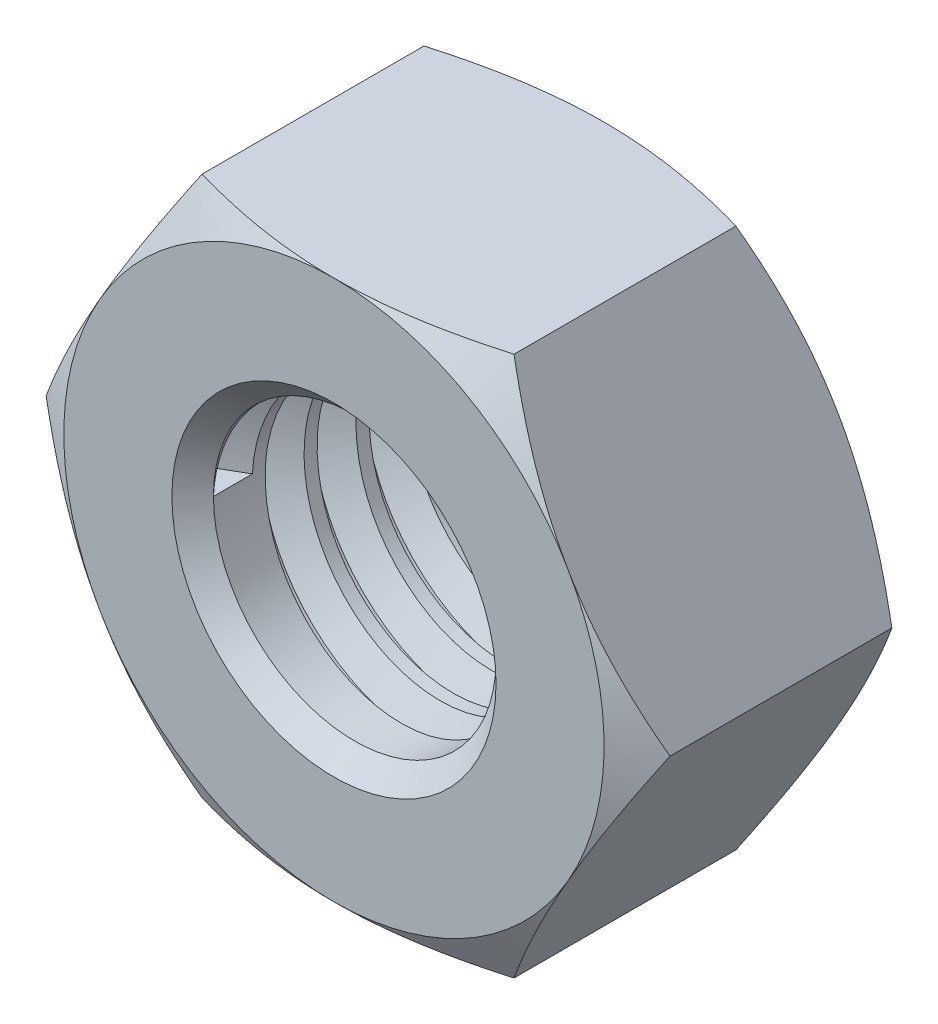
SolidWorks part; units mm, degrees
material "AISI 304"
ref_plane "Front" through (0, 0, 0) normal (0, 0, 1) x (1, 0, 0)
ref_plane "Top" through (0, 0, 0) normal (0, 1, 0) x (1, 0, 0)
ref_plane "Right" through (0, 0, 0) normal (1, 0, 0) x (0, 0, -1)
sketch "Sketch2" plane through (0, 0, 0) normal (0, 0, 1) x (1, 0, 0)
  line L1 (-3.7528, 6.5) -> (-7.5056, 0)
  line L2 (-7.5056, 0) -> (-3.7528, -6.5)
  line L3 (-3.7528, -6.5) -> (3.7528, -6.5)
  line L4 (3.7528, -6.5) -> (7.5056, 0)
  line L5 (7.5056, 0) -> (3.7528, 6.5)
  line L6 (3.7528, 6.5) -> (-3.7528, 6.5)
  circle A0 centre (0, 0) radius 3.4
  circle A1 centre (0, 0) radius 6.5 construction
  dimension "D1" = 6.8
  dimension "D2" = 13
extrude "Boss-Extrude1" add sketch "Sketch2" along normal blind 6.5
sketch "Sketch3" plane through (0, 0, 0) normal (1, 0, 0) x (0, 0, -1)
  line L0 (0, 6.5) -> (0, 9.5)
  line L1 (0, 9.5) -> (-1.7321, 9.5)
  line L2 (-1.7321, 9.5) -> (0, 6.5)
  line L3 (-6.5, 6.5) -> (-6.5, 9.5)
  line L4 (-6.5, 9.5) -> (-4.7679, 9.5)
  line L5 (-4.7679, 9.5) -> (-6.5, 6.5)
  dimension "D1" = 30
  dimension "D2" = 3
ref_axis "Axis1" through (0, 0, 6.5) along (0, 0, -1)
revolve "Cut-Revolve1" cut sketch "Sketch3" angle 360 about axis through (0, 0, 6.5) along (0, 0, -1)
chamfer "Chamfer1" distance 0.5 angle 45 2 edges at (3.4, 0, 6.5) (3.4, 0, 0)
thread "Thread1" pitch 1.25 method cut profile "Thread Profile1" start angle 0, offset 0, length 0, pitch 1.25, diameter 6.8
ref_plane "Plane1" through (-3.4, 0, 6) normal (0, -1, 0) x (-1, 0, 0)
sketch "Thread Profile1" plane through (-3.4, 0, 6) normal (0, -1, 0) x (-1, 0, 0)
  line L0 (0, 0) -> (0, 1.25) construction
  line L1 (0, 0) -> (0.6766, 0.3906)
  line L2 (0.6766, 0.3906) -> (0.6766, 0.5469)
  line L3 (0.6766, 0.5469) -> (0, 0.9375)
  line L4 (0.6766, 0.4687) -> (0, 0.4687) construction
  line L11 (0, 0) -> (0, 0.9375)
  point P2 (0, 0)
  dimension "Pitch" = 1.25
  dimension "Profile_Angle" = 60
  dimension "Profile_Land" = 0.1562
  dimension "Profile_Height" = 0.6766
